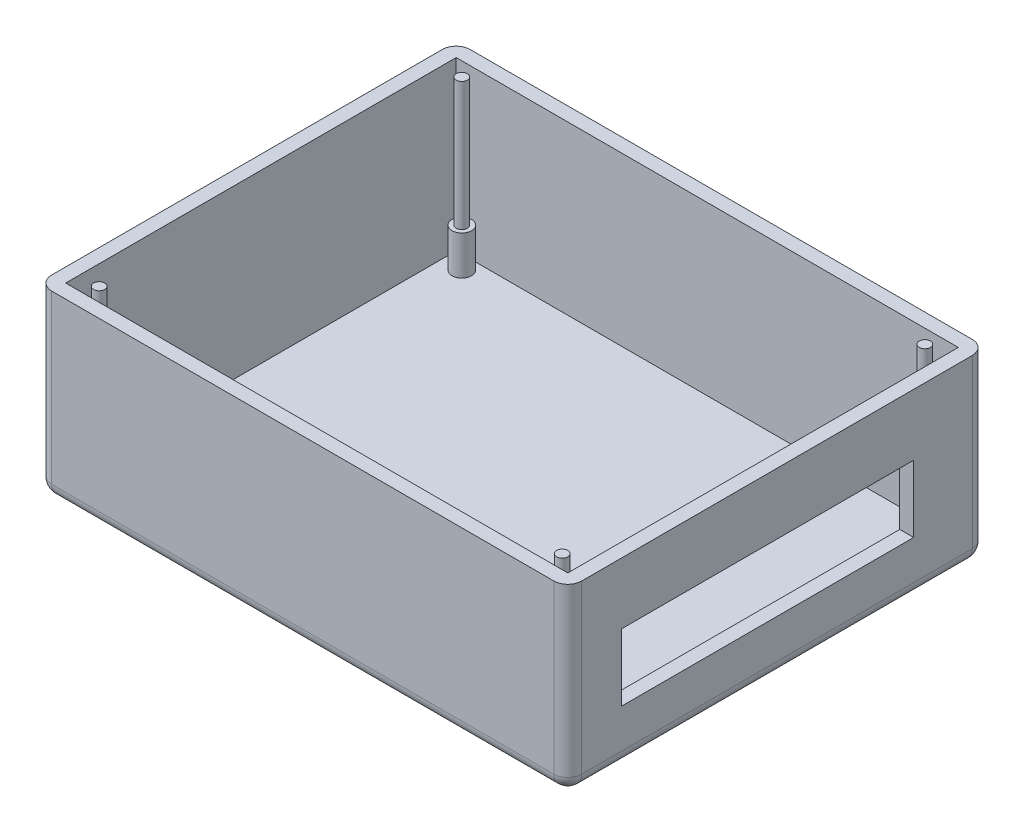
SolidWorks part; units mm, degrees
ref_plane "Front Plane" through (0, 0, 0) normal (0, 0, 1) x (1, 0, 0)
ref_plane "Top Plane" through (0, 0, 0) normal (0, 1, 0) x (1, 0, 0)
ref_plane "Right Plane" through (0, 0, 0) normal (1, 0, 0) x (0, 0, -1)
sketch "Sketch1" plane through (0, 0, 0) normal (0, 1, 0) x (1, 0, 0)
  line L1 (-47.5, 37.5) -> (47.5, 37.5)
  line L2 (-47.5, 37.5) -> (-47.5, -37.5)
  line L3 (-47.5, -37.5) -> (47.5, -37.5)
  line L4 (47.5, 37.5) -> (47.5, -37.5)
  point P4 (0, 37.5)
  point P7 (0, -37.5)
  point P8 (47.5, 0)
  point P9 (-47.5, 0)
  dimension "D1" = 75
  dimension "D2" = 95
extrude "Boss-Extrude1" add sketch "Sketch1" along normal blind 32.5
sketch "Sketch2" plane through (0, 32.5, 0) normal (0, 1, 0) x (1, 0, 0)
  line L0 (47.5, 37.5) -> (-47.5, 37.5) construction
  line L1 (-45, 35) -> (45, 35)
  line L2 (-45, 35) -> (-45, -35)
  line L3 (-45, -35) -> (45, -35)
  line L4 (45, 35) -> (45, -35)
  line L5 (-47.5, -37.5) -> (47.5, -37.5) construction
  line L6 (47.5, -37.5) -> (47.5, 37.5) construction
  line L7 (-47.5, 37.5) -> (-47.5, -37.5) construction
  dimension "D1" = 2.5
  dimension "D2" = 2.5
  dimension "D3" = 2.5
  dimension "D4" = 2.5
extrude "Cut-Extrude1" cut sketch "Sketch2" against normal blind 30
sketch "Sketch3" plane through (0, 2.5, 0) normal (0, 1, 0) x (1, 0, 0)
  line L0 (-45, 35) -> (-45, -35) construction
  line L1 (45, 35) -> (-45, 35) construction
  line L2 (45, -35) -> (45, 35) construction
  line L3 (45, 35) -> (-45, 35) construction
  line L4 (45, -35) -> (45, 35) construction
  line L5 (-45, -35) -> (45, -35) construction
  line L6 (-45, -35) -> (45, -35) construction
  circle A0 centre (-41.5, 32.5) radius 1.75
  circle A1 centre (41.5, 32.5) radius 1.75
  circle A2 centre (41.5, -32.5) radius 1.75
  circle A3 centre (-41.5, -32.5) radius 1.75
  point P12 (40.1836, 7.9735)
  point P13 (30.9105, -27.0818)
  point P14 (33.7908, 18.1599)
  point P19 (0, 0)
  dimension "D3" = 3.5
  dimension "D6" = 3.5
  dimension "D9" = 3.5
  dimension "D12" = 3.5
  dimension "D1" = 3.5
  dimension "D2" = 2.5
  dimension "D4" = 3.5
  dimension "D5" = 2.5
  dimension "D7" = 3.5
  dimension "D8" = 2.5
  dimension "D10" = 3.5
  dimension "D11" = 2.5
extrude "Boss-Extrude2" add sketch "Sketch3" along normal blind 7
sketch "Sketch4" plane through (0, 9.5, 0) normal (0, 1, 0) x (1, 0, 0)
  circle A0 centre (-41.5, 32.5) radius 1
  circle A1 centre (41.5, 32.5) radius 1
  circle A2 centre (41.5, -32.5) radius 1
  circle A3 centre (-41.5, -32.5) radius 1
  dimension "D1" = 2
  dimension "D2" = 2
  dimension "D3" = 2
  dimension "D4" = 2
extrude "Boss-Extrude3" add sketch "Sketch4" along normal up to surface (23 mm away) up to face at (0, 32.5, 0)
sketch "Sketch5" plane through (47.5, 0, 0) normal (1, 0, 0) x (0, 0, -1)
  line L0 (-37.5, 0) -> (37.5, 0) construction
  line L1 (-27.8482, 21.5) -> (24.5, 21.5)
  line L2 (-27.8482, 21.5) -> (-27.8482, 9.5)
  line L3 (-27.8482, 9.5) -> (24.5, 9.5)
  line L4 (24.5, 21.5) -> (24.5, 9.5)
  line L5 (-37.5, 32.5) -> (-37.5, 0) construction
  line L6 (37.5, 32.5) -> (37.5, 0) construction
  dimension "D1" = 9.5
  dimension "D2" = 9.6518
  dimension "D3" = 13
  dimension "D4" = 12
extrude "Cut-Extrude2" cut sketch "Sketch5" against normal blind 7
fillet "Fillet1" radius 2.5 4 edges at (-47.5, 0, 0) (0, 0, 37.5) (47.5, 0, 0) (0, 0, -37.5) type face fillet first side face at (0, 16.25, 37.5) first side face at (47.5, 15.5, 1.6741) first side face at (-47.5, 16.25, 0) first side face at (0, 16.25, -37.5) second side face at (0, 0, 0)
fillet "Fillet2" radius 2.5 1 edges at (47.5, 17.5, 37.5) type face fillet first side face at (0, 17.5, 37.5) second side face at (47.5, 15.5, 1.6741)
fillet "Fillet3" radius 2.5 1 edges at (47.5, 17.5, -37.5) type face fillet first side face at (47.5, 15.5, 1.6741) second side face at (0, 17.5, -37.5)
fillet "Fillet4" radius 2.5 1 edges at (-47.5, 17.5, -37.5) type face fillet first side face at (-1.25, 17.5, -37.5) second side face at (-47.5, 17.5, 0)
fillet "Fillet5" radius 2.5 1 edges at (-47.5, 17.5, 37.5) type face fillet first side face at (-47.5, 17.5, 1.25) second side face at (-1.25, 17.5, 37.5)
